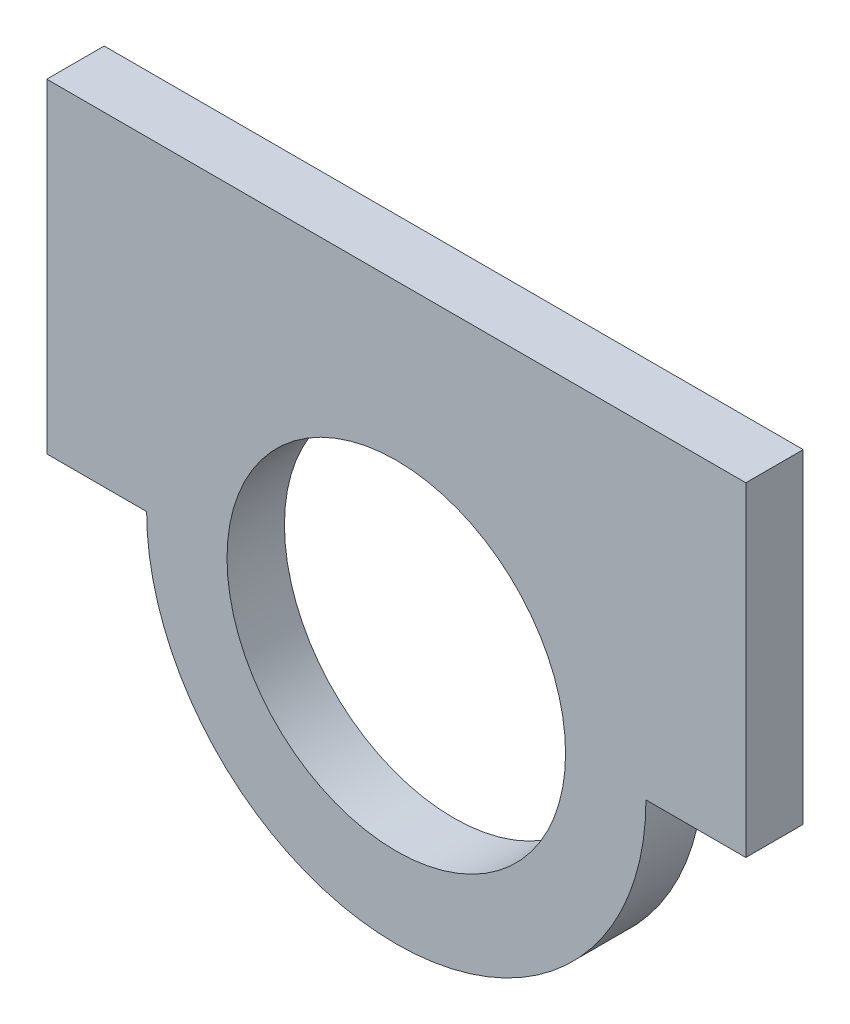
SolidWorks part; units mm, degrees
ref_plane "Спереди" through (0, 0, 0) normal (0, 0, 1) x (1, 0, 0)
ref_plane "Сверху" through (0, 0, 0) normal (0, 1, 0) x (1, 0, 0)
ref_plane "Справа" through (0, 0, 0) normal (1, 0, 0) x (0, 0, -1)
sketch "Эскиз1" plane through (0, 0, 0) normal (0, 0, 1) x (1, 0, 0)
  line L0 (-70, 65) -> (70, 65)
  line L1 (70, 65) -> (70, 0)
  line L2 (70, 0) -> (50, 0)
  line L4 (-50, 0) -> (-70, 0)
  line L5 (-70, 0) -> (-70, 65)
  circle A0 centre (0, 0) radius 33.9
  circle A1 centre (0, 0) radius 50
  point P11 (-72.1342, 78.276)
  dimension "D1" = 67.8
  dimension "D2" = 100
  dimension "D3" = 65
  dimension "D4" = 20
extrude "Бобышка-Вытянуть1" add sketch "Эскиз1" along normal blind 11.5 contours A1 A0 | A1 L2 L1 L0 L5 L4 region at (0, 63.4565, 0) region at (0, 48.5858, 0)
